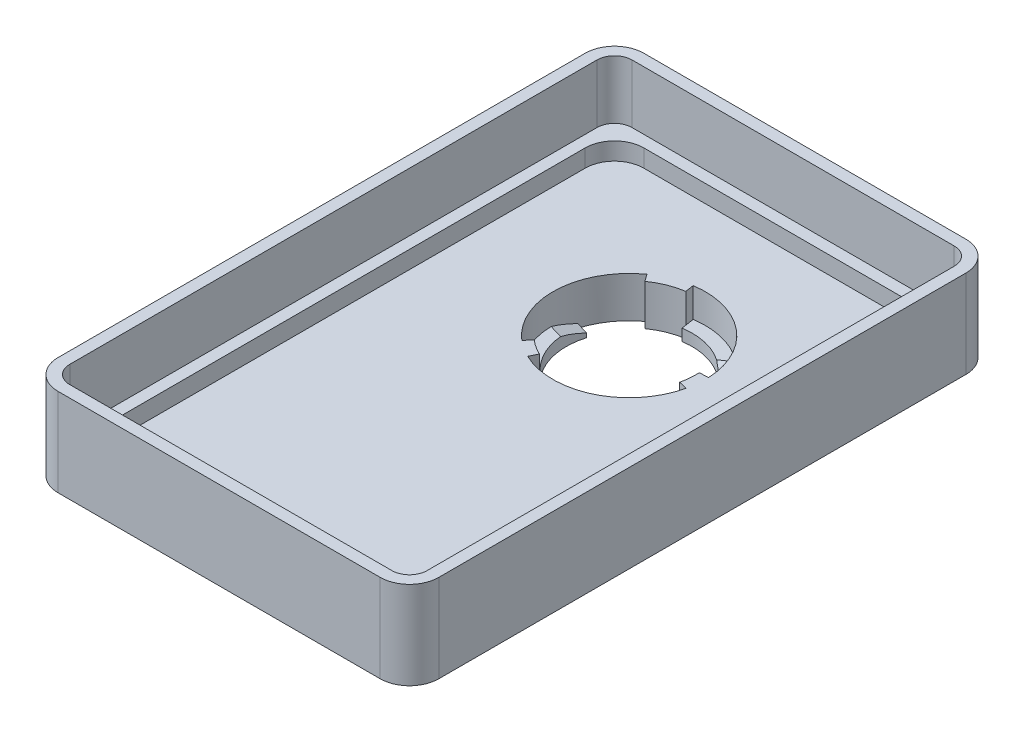
SolidWorks part; units mm, degrees
ref_plane "Front Plane" through (0, 0, 0) normal (0, 0, 1) x (1, 0, 0)
ref_plane "Top Plane" through (0, 0, 0) normal (0, 1, 0) x (1, 0, 0)
ref_plane "Right Plane" through (0, 0, 0) normal (1, 0, 0) x (0, 0, -1)
sketch "Sketch1" plane through (0, 0, 0) normal (0, 1, 0) x (1, 0, 0)
  line L1 (-32.5, 30) -> (32.5, 30)
  line L2 (-32.5, 30) -> (-32.5, -70)
  line L3 (-32.5, -70) -> (32.5, -70)
  line L4 (32.5, 30) -> (32.5, -70)
  line L5 (-32.5, 0) -> (32.5, 0) construction
  point P4 (0, 0)
  dimension "D1" = 65
  dimension "D2" = 100
  dimension "D3" = 30
extrude "Boss-Extrude1" add sketch "Sketch1" along normal blind 2
sketch "Sketch2" plane through (0, 2, 0) normal (0, 1, 0) x (1, 0, 0)
  line L14 (-28.5, -66) -> (28.5, -66)
  line L15 (28.5, -66) -> (28.5, 26)
  line L16 (-28.5, 26) -> (-28.5, -66)
  line L17 (28.5, 26) -> (-28.5, 26)
  line L18 (-28.5, -66) -> (28.5, -66)
  line L19 (28.5, -66) -> (28.5, 26)
  line L20 (-28.5, 26) -> (-28.5, -66)
  line L21 (28.5, 26) -> (-28.5, 26)
  line L32 (-32.5, -70) -> (32.5, -70)
  line L33 (-32.5, 30) -> (-32.5, -70)
  line L34 (32.5, -70) -> (32.5, 30)
  line L35 (32.5, 30) -> (-32.5, 30)
  line L36 (-32.5, -70) -> (32.5, -70)
  line L37 (-32.5, 30) -> (-32.5, -70)
  line L38 (32.5, -70) -> (32.5, 30)
  line L39 (32.5, 30) -> (-32.5, 30)
  dimension "D1" = 4
  dimension "D2" = 0
extrude "Boss-Extrude2" add sketch "Sketch2" along normal blind 3
fillet "Fillet1" radius 5 8 edges at (28.5, 3.5, 66) (-28.5, 3.5, 66) (28.5, 3.5, -26) (-28.5, 3.5, -26) (-32.5, 2.5, 70) (32.5, 2.5, 70) (-32.5, 2.5, -30) (32.5, 2.5, -30)
sketch "Sketch4" plane through (0, 5, 0) normal (0, 1, 0) x (1, 0, 0)
  line L4 (-32.5, 25) -> (-32.5, -65)
  line L5 (-27.5, -70) -> (27.5, -70)
  line L6 (32.5, -65) -> (32.5, 25)
  line L7 (27.5, 30) -> (-27.5, 30)
  line L8 (-30.5, 25) -> (-30.5, -65)
  line L9 (-27.5, -68) -> (27.5, -68)
  line L10 (30.5, -65) -> (30.5, 25)
  line L11 (27.5, 28) -> (-27.5, 28)
  line L12 (-30.5, 25) -> (-30.5, -65)
  line L13 (-27.5, -68) -> (27.5, -68)
  line L14 (30.5, -65) -> (30.5, 25)
  line L15 (27.5, 28) -> (-27.5, 28)
  arc A4 (-32.5, -65) -> (-27.5, -70) centre (-27.5, -65) ccw
  arc A5 (27.5, -70) -> (32.5, -65) centre (27.5, -65) ccw
  arc A6 (32.5, 25) -> (27.5, 30) centre (27.5, 25) ccw
  arc A7 (-27.5, 30) -> (-32.5, 25) centre (-27.5, 25) ccw
  arc A8 (-30.5, -65) -> (-27.5, -68) centre (-27.5, -65) ccw
  arc A9 (27.5, -68) -> (30.5, -65) centre (27.5, -65) ccw
  arc A10 (30.5, 25) -> (27.5, 28) centre (27.5, 25) ccw
  arc A11 (-27.5, 28) -> (-30.5, 25) centre (-27.5, 25) ccw
  arc A12 (-30.5, -65) -> (-27.5, -68) centre (-27.5, -65) ccw
  arc A13 (27.5, -68) -> (30.5, -65) centre (27.5, -65) ccw
  arc A14 (30.5, 25) -> (27.5, 28) centre (27.5, 25) ccw
  arc A15 (-27.5, 28) -> (-30.5, 25) centre (-27.5, 25) ccw
  dimension "D1" = 2
  dimension "D2" = 2
extrude "Boss-Extrude3" add sketch "Sketch4" along normal blind 10
ref_plane "Plane1" through (0, -5, 0) normal (0, -1, 0) x (-1, 0, 0)
sketch "Sketch6" plane through (0, -5, 0) normal (0, -1, 0) x (-1, 0, 0)
  circle A0 centre (0, 0) radius 18
  dimension "D1" = 36
extrude "Boss-Extrude4" add sketch "Sketch6" against normal up to surface (5 mm away) up to face at (0, 0, 20)
chamfer "Chamfer1" distance 10 angle 45 1 edges at (0, 0, 18)
sketch "Sketch7" plane through (0, -5, 0) normal (0, -1, 0) x (1, 0, 0)
  circle A0 centre (0, 0) radius 13
  dimension "D1" = 26
extrude "Cut-Extrude1" cut sketch "Sketch7" against normal through all
sketch "Sketch8" plane through (0, -5, 0) normal (0, -1, 0) x (-1, 0, 0)
  line L0 (0, 0) -> (1.6998, 11.3737)
  line L1 (0, 0) -> (11.0264, 3.2662) construction
  line L2 (0, 0) -> (6.6781, 9.3623) construction
  line L3 (0, 0) -> (1.2021, 11.437) construction
  line L4 (0, 0) -> (12.4647, 3.6922)
  line L5 (0, 0) -> (7.5491, 10.5835)
  line L6 (0, 0) -> (5.5966, -11.7336)
  line L7 (0, 0) -> (-2.4805, -12.7612)
  line L8 (0, 0) -> (-12.9876, 0.5671)
  line L9 (0, 0) -> (-10.7838, 7.2601)
  line L10 (0, 0) -> (8.4428, -9.8853)
  line L11 (0, 0) -> (-12.6668, -2.9244)
  line L12 (1.6998, 11.3737) -> (1.9215, 12.8572)
  circle A0 centre (0, 0) radius 10.75
  circle A1 centre (0, 0) radius 11.5
  circle A2 centre (0, 0) radius 13
  circle A3 centre (0, 0) radius 13 construction
  point P7 (0, 0)
extrude "Boss-Extrude6" add sketch "Sketch8" against normal blind 2 contours L12 A2 L9 A1 | L5 A2 L12 A1 | L10 A2 L4 A1 | L6 A2 L10 A1 | L0 A1 L9 A0 | L10 A1 L4 A0 | L11 A2 L7 A1 | L11 A1 L7 A0 | L8 A2 L11 A1 region at (4.3842, -5, -9.9522) region at (-10.7033, -5, -3.0366) region at (2.2479, -5, 10.8963) region at (4.6873, -5, -10.6402) region at (-4.5523, -5, -11.2673) region at (-11.1207, -5, 3.2941) region at (-6.6611, -5, 10.2572) region at (8.0569, -5, 8.3431) region at (12.1766, -5, 1.1189)
extrude "Boss-Extrude7" add sketch "Sketch8<5>" against normal up to surface (7 mm away) contours L5 A2 L12 A1 | L6 A2 L10 A1 | L8 A2 L11 A1 region at (-4.5523, -5, -11.2673) region at (-6.6611, -5, 10.2572) region at (12.1766, -5, 1.1189) up to face at (0, 2, 13)
sketch "Sketch8<5>" plane through (0, -5, 0) normal (0, -1, 0) x (-1, 0, 0) same geometry as "Sketch8"
chamfer "Chamfer2" distance 1.3 angle 72 3 edges at (2.2659, -3, 11.6568) (-11.386, -3, -3.3727) (9.8506, -3, -6.6319) first distance on face at (2.2659, -4, 11.6568) first distance on face at (-11.386, -4, -3.3727) first distance on face at (9.8506, -4, -6.6319)
